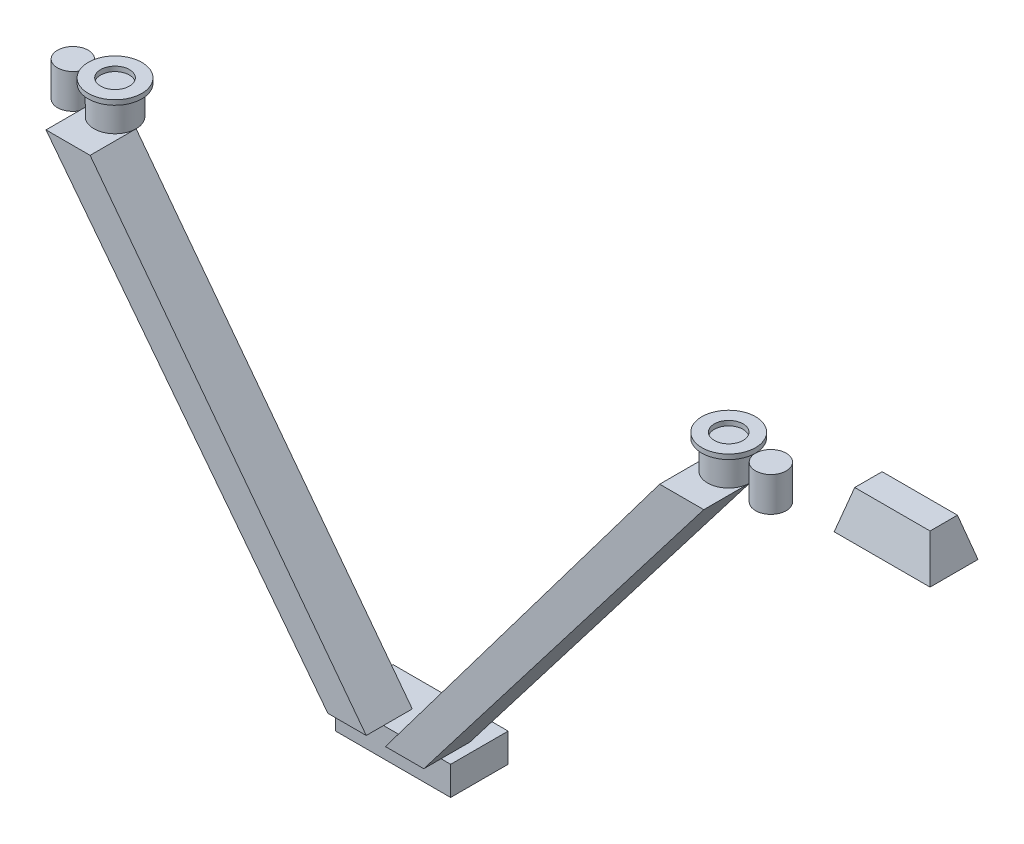
SolidWorks part; units mm, degrees
ref_plane "Front Plane" through (0, 0, 0) normal (0, 0, 1) x (1, 0, 0)
ref_plane "Top Plane" through (0, 0, 0) normal (0, 1, 0) x (1, 0, 0)
ref_plane "Right Plane" through (0, 0, 0) normal (1, 0, 0) x (0, 0, -1)
other "Configuration Table"
sketch "Sketch1" plane through (0, 0, 0) normal (0, 1, 0) x (1, 0, 0)
  circle A0 centre (-1600, 0) radius 140
  circle A1 centre (-1600, 0) radius 75
extrude "Boss-Extrude1" add sketch "Sketch1" against normal blind 25 from offset 3325 flip side to cut
sketch "Sketch2" plane through (0, 0, 0) normal (0, 1, 0) x (1, 0, 0)
  circle A0 centre (-1600, 0) radius 110
extrude "Boss-Extrude2" add sketch "Sketch2" against normal blind 150 from offset 3300 flip side to cut
sketch "Sketch3" plane through (0, 0, 0) normal (0, 1, 0) x (1, 0, 0)
  circle A0 centre (-1820, 0) radius 80
extrude "Boss-Extrude3" add sketch "Sketch3" along normal blind 180 from offset 3120
sketch "Sketch4" plane through (0, 0, 0) normal (0, 1, 0) x (1, 0, 0)
  circle A0 centre (1600, 0) radius 140
  circle A1 centre (1600, 0) radius 75
extrude "Boss-Extrude4" add sketch "Sketch4" against normal blind 25 from offset 3325 flip side to cut
sketch "Sketch5" plane through (0, 0, 0) normal (0, 1, 0) x (1, 0, 0)
  circle A0 centre (1600, 0) radius 110
extrude "Boss-Extrude5" add sketch "Sketch5" against normal blind 150 from offset 3300 flip side to cut
sketch "Sketch6" plane through (0, 0, 0) normal (0, 1, 0) x (1, 0, 0)
  circle A0 centre (1820, 0) radius 80
extrude "Boss-Extrude6" add sketch "Sketch6" along normal blind 180 from offset 3120
sketch "Sketch7" plane through (0, 0, 0) normal (0, 0, 1) x (1, 0, 0)
  line L0 (-1720, 3150) -> (-1490, 3150)
  line L1 (-1710, 3150) -> (-1490, 3150) construction
  line L2 (-1490, 3150) -> (-50, 1250)
  line L3 (-50, 1250) -> (-250, 1250)
  line L4 (-250, 1250) -> (-1720, 3150)
extrude "Boss-Extrude7" add sketch "Sketch7" along normal blind 240
sketch "Sketch8" plane through (0, 0, 0) normal (0, 0, 1) x (1, 0, 0)
  line L0 (1480, 3150) -> (1710, 3150)
  line L1 (1490, 3150) -> (1710, 3150) construction
  line L2 (1710, 3150) -> (250, 1250)
  line L3 (250, 1250) -> (50, 1250)
  line L4 (50, 1250) -> (1480, 3150)
extrude "Boss-Extrude8" add sketch "Sketch8" along normal blind 240
sketch "Sketch9" plane through (0, 0, 0) normal (0, 1, 0) x (1, 0, 0)
  line L1 (-300, -150) -> (300, -150)
  line L2 (-300, -150) -> (-300, 150)
  line L3 (-300, 150) -> (300, 150)
  line L4 (300, -150) -> (300, 150)
extrude "Boss-Extrude9" add sketch "Sketch9" along normal blind 150 from offset 1100
sketch "Sketch10" plane through (0, 0, 0) normal (0, 1, 0) x (1, 0, 0)
  line L1 (-250, 2400) -> (250, 2400)
  line L2 (-250, 2400) -> (-250, 2650)
  line L3 (-250, 2650) -> (250, 2650)
  line L4 (250, 2400) -> (250, 2650)
extrude "Boss-Extrude10" add sketch "Sketch10" along normal blind 200 draft 15 from offset 750
